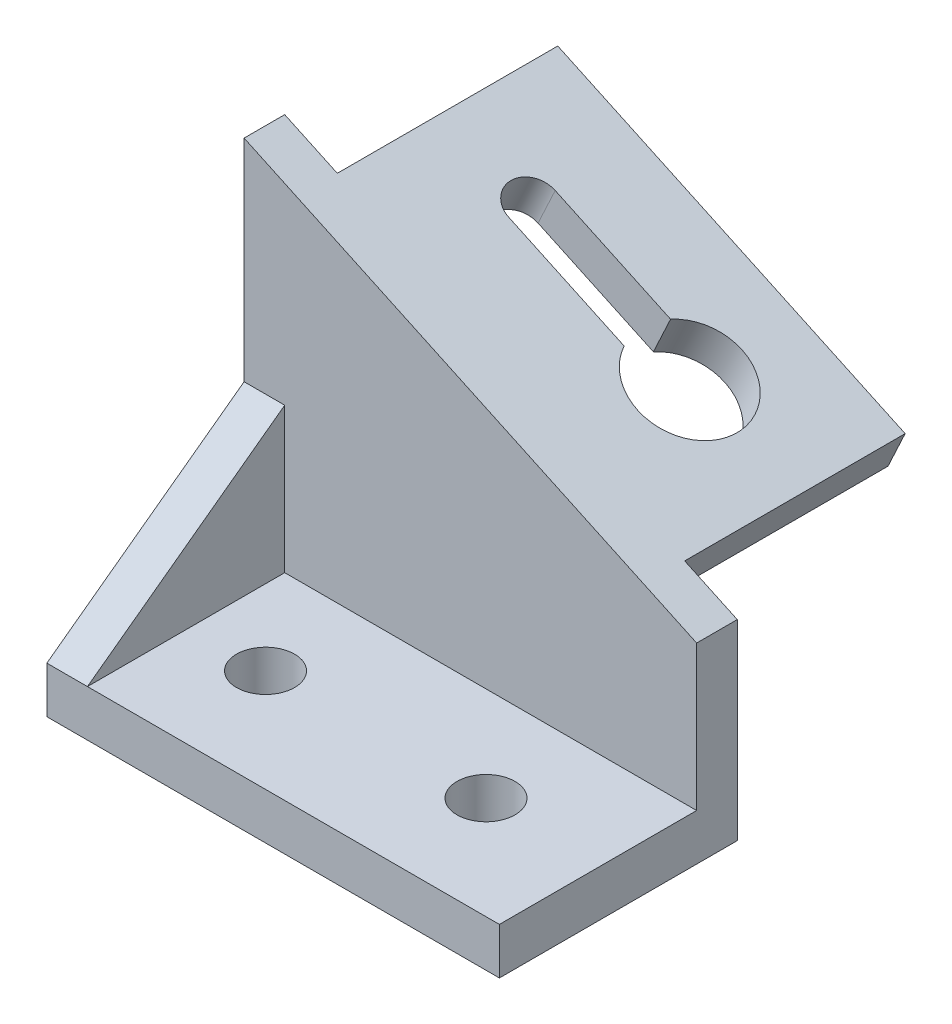
SolidWorks part; units mm, degrees
ref_plane "Front Plane" through (0, 0, 0) normal (0, 0, 1) x (1, 0, 0)
ref_plane "Top Plane" through (0, 0, 0) normal (0, 1, 0) x (1, 0, 0)
ref_plane "Right Plane" through (0, 0, 0) normal (1, 0, 0) x (0, 0, -1)
sketch "Sketch1" plane through (0, 0, 0) normal (0, 1, 0) x (1, 0, 0)
  line L0 (0, 0) -> (78, 0)
  line L1 (78, 0) -> (78, 41)
  line L2 (78, 41) -> (0, 41)
  line L3 (0, 41) -> (0, 0)
  line L4 (78, 34) -> (0, 34)
  line L5 (7, 34) -> (7, 0)
  circle A0 centre (20, 17.6951) radius 5
  circle A1 centre (58, 17.6951) radius 5
  dimension "D5" = 20
  dimension "D1" = 78
  dimension "D2" = 41
  dimension "D3" = 7
  dimension "D4" = 7
  dimension "D6" = 20
extrude "Boss-Extrude1" add sketch "Sketch1" along normal blind 8 contours L4 L5 L0 L1 A1 A0 region at (42.7436, 0, -16.9516)
extrude "Boss-Extrude2" add sketch "Sketch1<3>" along normal blind 33 contours L5 L4 L3 L0 region at (3.5, 0, -17)
sketch "Sketch1<3>" plane through (0, 0, 0) normal (0, 1, 0) x (1, 0, 0) same geometry as "Sketch1"
extrude "Boss-Extrude3" add sketch "Sketch1<4>" along normal blind 80 contours L4 L1 L2 L3 region at (39, 0, -37.5)
sketch "Sketch1<4>" plane through (0, 0, 0) normal (0, 1, 0) x (1, 0, 0) same geometry as "Sketch1"
sketch "Sketch2" plane through (0, 0, -34) normal (0, 0, 1) x (1, 0, 0)
  line L0 (78, 8) -> (78, 33)
  line L1 (78, 80) -> (78, 8) construction
  line L2 (78, 33) -> (-0.0333, 69.3875)
  line L3 (0, 0) -> (78, 0) construction
  line L4 (-0.0333, 69.3875) -> (0, 80)
  line L5 (0, 80) -> (78, 80)
  line L6 (78, 80) -> (78, 33)
  line M6 (78, 8) -> (78, 80)
  line M7 (78, 80) -> (0, 80)
  line M8 (0, 80) -> (0, 33)
  dimension "D1" = 25
  dimension "D2" = 25
extrude "Cut-Extrude1" cut sketch "Sketch2" against normal blind 80 contours L2 M6 M7 M8 region at (47.205, 63.68, -34)
sketch "Sketch3" plane through (26.571, 56.9817, 0) normal (0.4226, 0.9063, 0) x (0.9063, -0.4226, 0)
  line L0 (-19.3179, 41) -> (-19.3179, 79)
  line L1 (56.7456, 41) -> (-29.3179, 41) construction
  line L2 (-19.3179, 79) -> (46.7456, 79)
  line L3 (46.7456, 79) -> (46.7456, 41)
  line L4 (-29.3179, 41) -> (-29.3179, 34) construction
  line L5 (56.7456, 41) -> (56.7456, 34) construction
  line L6 (56.7456, 34) -> (-29.3179, 34) construction
  line L7 (-23.8983, 60) -> (50.7384, 60) construction
  line L8 (-3.2544, 64) -> (18.6833, 64)
  line L9 (-3.2544, 56) -> (18.6833, 56)
  arc A0 (-3.2544, 64) -> (-3.2544, 56) centre (-3.2544, 60) ccw
  arc A1 (18.6833, 56) -> (18.6833, 64) centre (26.7456, 60) ccw
  point P20 (17.167, 64.0266)
  point P23 (17.167, 55.04)
  point P24 (-19.3179, 60)
  line M9 (56.7456, 41) -> (-29.3179, 41)
  dimension "D4" = 8
  dimension "D5" = 18
  dimension "D1" = 10
  dimension "D2" = 10
  dimension "D3" = 45
  dimension "D6" = 30
  dimension "D7" = 20
extrude "Boss-Extrude4" add sketch "Sketch3" against normal blind 7 contours L0 L7 A0 L8 A1 L3 L2 | L7 L0 L3 A1 L9 A0 M9 region at (38.221, 51.5492, -49.084) region at (38.221, 51.5492, -70.916)
chamfer "Chamfer1" distance 25 distance2 34 1 edges at (3.5, 33, 0) first distance on face at (28.3333, 13.6667, 0)
